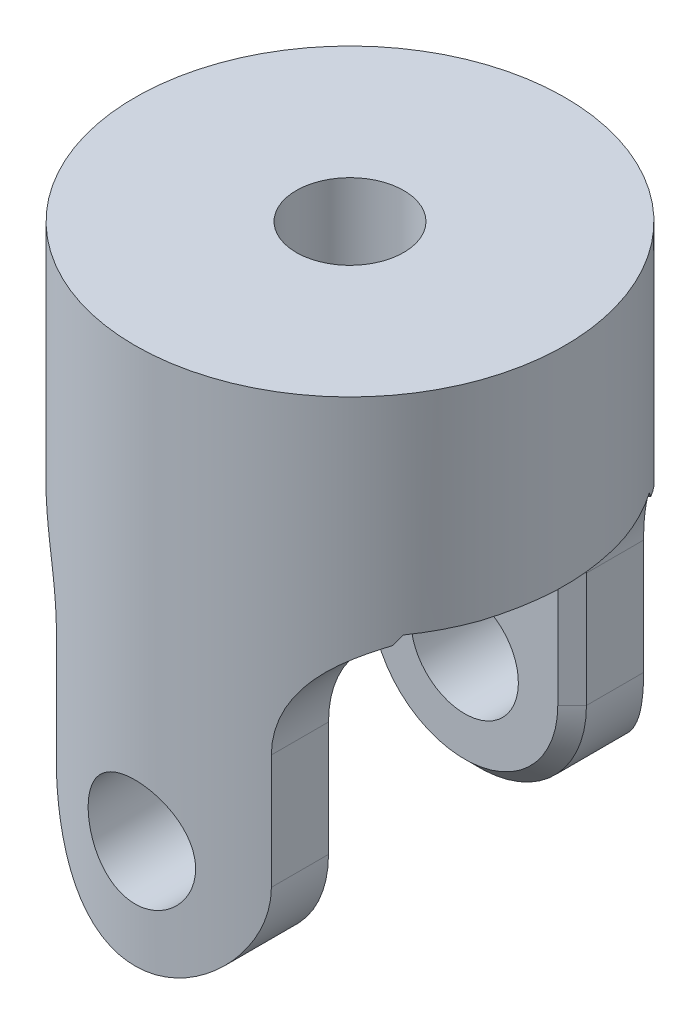
SolidWorks part; units mm, degrees
ref_plane "Front" through (0, 0, 0) normal (0, 0, 1) x (1, 0, 0)
ref_plane "Top" through (0, 0, 0) normal (0, 1, 0) x (-1, 0, 0)
ref_plane "Right" through (0, 0, 0) normal (1, 0, 0) x (0, 0, -1)
sketch "Sketch1" plane through (0, 0, 0) normal (0, 1, 0) x (-1, 0, 0)
  circle A0 centre (0, 0) radius 19.05
  dimension "D1" = 38.1
extrude "Base-Extrude" add sketch "Sketch1" along normal blind 47.625
sketch "Sketch2" plane through (0, 0, 0) normal (0, 0, 1) x (1, 0, 0)
  line L0 (0, 0) -> (0, 23.7435) construction
  line L1 (9.525, 9.525) -> (9.525, 19.685)
  line L2 (-9.525, 9.525) -> (-9.525, 19.685)
  line L3 (19.05, 29.21) -> (19.05, 0)
  line L4 (-19.05, 47.625) -> (-19.05, 0) construction
  line L5 (-19.05, 0) -> (-19.05, 29.21)
  line L6 (19.05, 0) -> (-19.05, 0) construction
  arc A0 (-9.525, 9.525) -> (9.525, 9.525) centre (0, 9.525) ccw
  arc A1 (9.525, 19.685) -> (19.05, 29.21) centre (19.05, 19.685) cw
  arc A2 (-9.525, 19.685) -> (-19.05, 29.21) centre (-19.05, 19.685) ccw
  dimension "D3" = 9.525
  dimension "D2" = 19.05
  dimension "D4" = 29.21
extrude "Cut-Extrude1" cut sketch "Sketch2" against normal through all and the other way through all flip side to cut
sketch "Sketch8" plane through (0, 0, 0) normal (1, 0, 0) x (0, 0, -1)
  line L0 (-19.05, 0) -> (19.05, 0) construction
  line L1 (-10.16, 0) -> (-10.16, 29.1452)
  line L2 (10.16, 29.1452) -> (-10.16, 29.1452)
  line L3 (10.16, 29.1452) -> (10.16, 0)
  line L4 (0, 0) -> (0, 14.3858) construction
  point P4 (0, 0)
  dimension "D1" = 29.1452
  dimension "D2" = 20.32
extrude "Cut-Extrude5" cut sketch "Sketch8" against normal through all and the other way through all flip side to cut
sketch "Sketch11" plane through (0, 0, 0) normal (0, 0, 1) x (1, 0, 0)
  circle A0 centre (0, 9.525) radius 4.7625
  dimension "D1" = 9.525
extrude "Cut-Extrude6" cut sketch "Sketch11" against normal through all and the other way through all
sketch "Sketch12" plane through (0, 47.625, 0) normal (0, 1, 0) x (-1, 0, 0)
  circle A0 centre (0, 0) radius 4.7625
  dimension "D1" = 9.525
extrude "Cut-Extrude7" cut sketch "Sketch12" against normal through all
ref_axis "Axis1" through (0, 97.625, 0) along (0, -1, 0)
chamfer "Chamfer1" distance 1.27 angle 45 10 edges at (11.3465, 25.287, -10.16) (9.525, 14.605, -10.16) (0, 0, -10.16) (-9.525, 14.605, -10.16) (-11.3465, 25.287, -10.16) (11.3465, 25.287, 10.16) (9.525, 14.605, 10.16) (0, 0, 10.16) (-9.525, 14.605, 10.16) (-11.3465, 25.287, 10.16)
